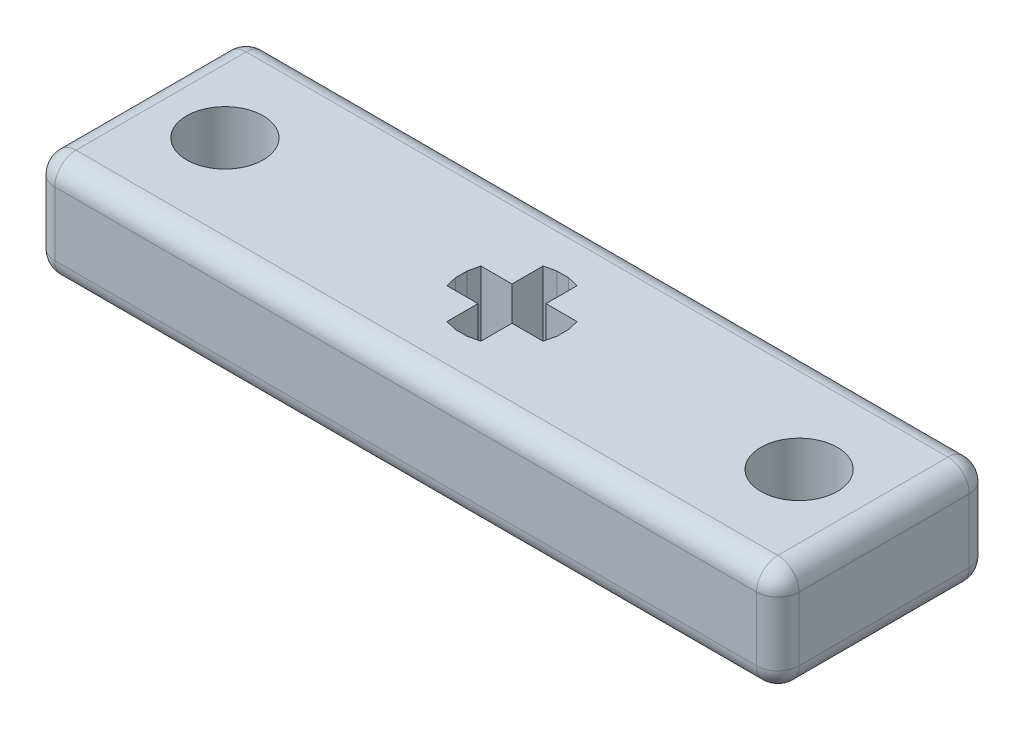
SolidWorks part; units mm, degrees
ref_plane "Front Plane" through (0, 0, 0) normal (0, 0, 1) x (1, 0, 0)
ref_plane "Top Plane" through (0, 0, 0) normal (0, 1, 0) x (1, 0, 0)
ref_plane "Right Plane" through (0, 0, 0) normal (1, 0, 0) x (0, 0, -1)
sketch "Sketch1" plane through (0, 0, 0) normal (0, 1, 0) x (1, 0, 0)
  line L0 (-0.8, 0.8) -> (-0.8, 2.2627)
  line L1 (-17.5, -5) -> (17.5, -5)
  line L2 (-17.5, -5) -> (-17.5, 5)
  line L3 (-17.5, 5) -> (17.5, 5)
  line L4 (17.5, -5) -> (17.5, 5)
  line L5 (-17.5, -5) -> (17.5, 5) construction
  line L6 (-17.5, 5) -> (17.5, -5) construction
  line L8 (-5, -5) -> (-5, 5)
  line L10 (5, -5) -> (5, 5)
  line L11 (-1.4286, -5) -> (1.4286, 5) construction
  line L12 (-1.4286, 5) -> (1.4286, -5) construction
  line L13 (-0.8, 2.2627) -> (-0.2701, 2.3847)
  line L14 (-0.2701, 2.3847) -> (0.2701, 2.3847)
  line L15 (0.2701, 2.3847) -> (0.8, 2.2627)
  line L16 (0.8, 2.2627) -> (0.8, 0.8)
  line L17 (0.8, 0.8) -> (2.2627, 0.8)
  line L18 (2.2627, 0.8) -> (2.3847, 0.2701)
  line L19 (2.3847, 0.2701) -> (2.3847, -0.2701)
  line L20 (2.3847, -0.2701) -> (2.2627, -0.8)
  line L21 (2.2627, -0.8) -> (0.8, -0.8)
  line L22 (0.8, -0.8) -> (0.8, -2.2627)
  line L23 (0.8, -2.2627) -> (0.2701, -2.3847)
  line L24 (0.2701, -2.3847) -> (-0.2701, -2.3847)
  line L25 (-0.2701, -2.3847) -> (-0.8, -2.2627)
  line L26 (-0.8, -2.2627) -> (-0.8, -0.8)
  line L27 (-0.8, -0.8) -> (-2.2627, -0.8)
  line L28 (-2.2627, -0.8) -> (-2.3847, -0.2701)
  line L29 (-2.3847, -0.2701) -> (-2.3847, 0.2701)
  line L30 (-2.3847, 0.2701) -> (-2.2627, 0.8)
  line L31 (-2.2627, 0.8) -> (-0.8, 0.8)
  circle A1 centre (0, 0) radius 3.5
  dimension "D3" = 10
  dimension "D4" = 35
  dimension "D5" = 10
extrude "Boss-Extrude1" add sketch "Sketch1" along normal blind 5 contours L1 L10 L3 L8 | L3 L10 L8 | L1 L8 L3 L2 | L10 L1 L8 | L2 L1 L4 L3 | L0 L13 L14 L15 L16 L17 L18 L19 L20 L21 L22 L23 L24 L25 L26 L27 L28 L29 L30 L31 region at (-11.25, 0, 0) region at (-4.8586, 0, 0)
fillet "Fillet4" radius 1 4 edges at (17.5, 2.5, -5) (17.5, 2.5, 5) (-17.5, 2.5, 5) (-17.5, 2.5, -5)
hole_wizard "M3 Clearance Hole1" positions "3DSketch1" profile "Sketch7" hole size "M3" standard "ANSI Metric" end condition through all
sketch3d "3DSketch1"
  line L0 (-16.5, 5, -5) -> (16.5, 5, -5) construction
  line L1 (-17.5, 5, 4) -> (-17.5, 5, -4) construction
  line L2 (-16.5, 5, 5) -> (16.5, 5, 5) construction
  line L3 (17.5, 5, 4) -> (17.5, 5, -4) construction
  point P0 (-13.5, 5, 0)
  point P2 (13.5, 5, 0)
  dimension "D1" = 5
  dimension "D2" = 4
  dimension "D3" = 5
  dimension "D4" = 4
sketch "Sketch7" plane through (-13.5, 5, 0) normal (1, 0, 0) x (0, 0, 1)
  line L0 (0, 0) -> (0, 5)
  line L1 (0, 5) -> (1.8, 5)
  line L2 (1.8, 5) -> (1.8, 0)
  line L5 (1.8, 0) -> (0, 0)
  line L11 (0, -6.35) -> (0, 107.95) construction
  dimension "Thru Hole Dia." = 3.6
  dimension "Thru Hole Depth" = 5
fillet "Fillet6" radius 1 16 edges at (-17.2071, 5, 4.7071) (0, 5, 5) (17.2071, 5, 4.7071) (17.2071, 5, -4.7071) (0, 5, -5) (-17.2071, 5, -4.7071) (-17.2071, 0, 4.7071) (0, 0, 5) (17.2071, 0, 4.7071) (17.2071, 0, -4.7071) (0, 0, -5) (-17.2071, 0, -4.7071) (17.5, 5, 0) (17.5, 0, 0) (-17.5, 5, 0) (-17.5, 0, 0)
